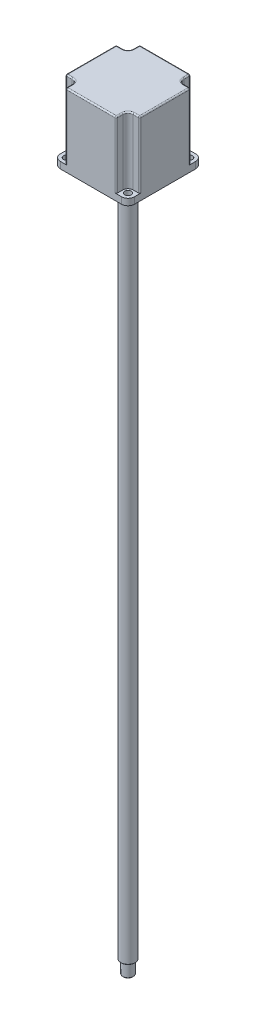
SolidWorks part; units mm, degrees
note: '?' marks a value the reader was unsure of.
material "1023 Carbon Steel Sheet (SS)"
ref_plane "Front" through (0, 0, 0) normal (0, 0, 1) x (1, 0, 0)
ref_plane "Top" through (0, 0, 0) normal (0, 1, 0) x (1, 0, 0)
ref_plane "Right" through (0, 0, 0) normal (1, 0, 0) x (0, 0, -1)
ref_axis "Axis1" through (-84.4107, 0, 0) along (1, 0, 0)?
ref_axis "Axis2" through (0, 64.3378, 0) along (0, -1, 0)?
ref_axis "Axis3" through (0, 0, -102.329) along (0, 0, 1)?
sketch "Sketch1" plane through (0, 0, 0) normal (0, 1, 0) x (1, 0, 0)
  line L1 (-28.5, -28.5) -> (28.5, -28.5)
  line L2 (-28.5, -28.5) -> (-28.5, 28.5)
  line L3 (-28.5, 28.5) -> (28.5, 28.5)
  line L4 (28.5, -28.5) -> (28.5, 28.5)
  line L5 (-28.5, -28.5) -> (28.5, 28.5) construction
  line L6 (-28.5, 28.5) -> (28.5, -28.5) construction
  point P0 (0, 0)
  dimension "D1" = 57
  dimension "D2" = 57
extrude "Extrude1" add sketch "Sketch1" along normal blind 76
hole_wizard "Ø5.0 (5) Diameter Hole1" positions "Sketch5" profile "Sketch4" hole size "Ø5.0" standard "ISO" end condition through all
sketch "Sketch5" plane through (0, 0, 0) normal (0, -1, 0) x (1, 0, 0)
  line L0 (-28.5, 28.5) -> (28.5, -28.5) construction
  line L3 (28.5, 28.5) -> (-28.5, -28.5) construction
  point P0 (-23.5, 23.5)
  point P1 (23.5, 23.5)
  point P3 (23.5, -23.5)
  point P5 (-23.5, -23.5)
  dimension "D1" = 47
  dimension "D2" = 47
sketch "Sketch4" plane through (-23.5, 0, 23.5) normal (1, 0, 0) x (0, 0, -1)
  line L0 (0, 0) -> (0, 76)
  line L1 (0, 76) -> (2.5, 76)
  line L2 (2.5, 76) -> (2.5, 0)
  line L5 (2.5, 0) -> (0, 0)
  line L11 (0, -6.35) -> (0, 107.95) construction
  dimension "Thru Hole Dia." = 5
  dimension "Thru Hole Depth" = 76
sketch "Sketch6" plane through (0, 76, 0) normal (0, 1, 0) x (1, 0, 0)
  line L0 (-19.5, 23.5) -> (-19.5, 32.5117)
  line L1 (-19.5, 32.5117) -> (-33.9089, 32.5117)
  line L2 (-33.9089, 32.5117) -> (-33.9089, 19.5)
  line L3 (-33.9089, 19.5) -> (-23.5, 19.5)
  line L4 (19.5, 23.5) -> (19.5, 36.4716)
  line L5 (19.5, 36.4716) -> (41.1684, 36.4716)
  line L6 (41.1684, 36.4716) -> (41.1684, 19.5)
  line L7 (41.1684, 19.5) -> (23.5, 19.5)
  line L8 (23.5, -19.5) -> (44.2522, -19.5)
  line L9 (44.2522, -19.5) -> (44.2522, -40.0504)
  line L10 (44.2522, -40.0504) -> (19.5, -40.0504)
  line L11 (19.5, -40.0504) -> (19.5, -23.5)
  line L12 (-23.5, -19.5) -> (-37.6708, -19.5)
  line L13 (-37.6708, -19.5) -> (-37.6708, -37.8282)
  line L14 (-37.6708, -37.8282) -> (-19.5, -37.8282)
  line L15 (-19.5, -37.8282) -> (-19.5, -23.5)
  circle A0 centre (-23.5, 23.5) radius 4
  circle A1 centre (23.5, 23.5) radius 4
  circle A2 centre (23.5, -23.5) radius 4
  circle A3 centre (-23.5, -23.5) radius 4
  circle M1 centre (-23.5, -23.5) radius 2.5
  circle M2 centre (23.5, -23.5) radius 2.5
  circle M3 centre (23.5, 23.5) radius 2.5
  circle M4 centre (-23.5, 23.5) radius 2.5
  line M5 (28.5, -28.5) -> (28.5, 28.5)
  line M6 (28.5, 28.5) -> (-28.5, 28.5)
  line M7 (-28.5, 28.5) -> (-28.5, -28.5)
  line M8 (-28.5, -28.5) -> (28.5, -28.5)
  dimension "D1" = 8
  dimension "D2" = 8
  dimension "D3" = 8
  dimension "D4" = 8
extrude "Extrude4" cut sketch "Sketch6" against normal blind 71 contours L2 L3 L0 L1 M7 M6 | A0 L0 L3 M6 M7 | A0 M4 | L7 L6 L5 L4 M6 M5 | A1 L7 L4 M5 M6 | A1 M3 | A2 M2 | A2 L11 L8 M8 M5 | L11 L10 L9 L8 M5 M8 | L14 L15 L12 L13 M8 M7 | A3 L12 L15 M7 M8 | A3 M1
fillet "Fillet1" radius 5 4 edges at (-28.5, 2.5, 28.5) (28.5, 2.5, 28.5) (28.5, 2.5, -28.5) (-28.5, 2.5, -28.5)
sketch "Sketch7" plane through (0, 76, 0) normal (0, 1, 0) x (1, 0, 0)
  circle A0 centre (0, 0) radius 3
  dimension "D1" = 6
extrude "Extrude5" add sketch "Sketch7" against normal blind 101 separate body
sketch "Sketch8" plane through (0, 0, 0) normal (0, -1, 0) x (1, 0, 0)
  circle A0 centre (0, 0) radius 19.05
  dimension "D1" = 38.1
extrude "Extrude6" add sketch "Sketch8" along normal blind 3
fillet "Fillet2" radius 1 24 edges at (-26, 76, 19.5) (-20.6716, 76, 20.6716) (-19.5, 76, 26) (0, 76, 28.5) (19.5, 76, 26) (20.6716, 76, 20.6716) (26, 76, 19.5) (28.5, 76, 0) (19.5, 76, -26) (26, 76, -19.5) (20.6716, 76, -20.6716) (-26, 76, -19.5) (-19.5, 76, -26) (-20.6716, 76, -20.6716) (0, 76, -28.5) (-28.5, 76, 0) (-19.5, 40.5, 28.5) (-28.5, 40.5, 19.5) (-28.5, 40.5, -19.5) (-19.5, 40.5, -28.5) (19.5, 40.5, -28.5) (28.5, 40.5, -19.5) (28.5, 40.5, 19.5) (19.5, 40.5, 28.5)
sketch "Sketch9" plane through (0, 0, 0) normal (0, -1, 0) x (1, 0, 0)
  circle A0 centre (0, 0) radius 5.5
  dimension "D1" = 11
extrude "Boss-Extrude1" add sketch "Sketch9" along normal blind 528
chamfer "Chamfer1" distance 0.5 angle 45 1 edges at (0, -528, -5.5)
sketch "Sketch10" plane through (0, -528, 0) normal (0, -1, 0) x (1, 0, 0)
  circle A0 centre (0, 0) radius 4
  dimension "D1" = 8
extrude "Boss-Extrude2" add sketch "Sketch10" along normal blind 10
chamfer "Chamfer2" distance 0.5 angle 45 1 edges at (0, -538, -4)
sketch "Sketch11" plane through (0, 0, 28.5) normal (0, 0, 1) x (1, 0, 0)
  line L0 (-23.5, 0) -> (23.5, 0) construction
  line L1 (42.7332, 56) -> (-106.5458, 56)
  line L2 (42.7332, 56) -> (42.7332, 147.9775)
  line L3 (42.7332, 147.9775) -> (-106.5458, 147.9775)
  line L4 (-106.5458, 56) -> (-106.5458, 147.9775)
  dimension "D1" = 56
extrude "Cut-Extrude1" cut sketch "Sketch11" against normal up to next
fillet "Fillet3" radius 1 24 edges at (19.2071, 56, 28.2071) (0, 56, 28.5) (-19.2071, 56, 28.2071) (-19.5, 56, 25.5) (-20.6716, 56, 20.6716) (-25.5, 56, 19.5) (-28.2071, 56, 19.2071) (-28.5, 56, 0) (-28.2071, 56, -19.2071) (-25.5, 56, -19.5) (-20.6716, 56, -20.6716) (-19.5, 56, -25.5) (-19.2071, 56, -28.2071) (0, 56, -28.5) (19.2071, 56, -28.2071) (19.5, 56, -25.5) (20.6716, 56, -20.6716) (25.5, 56, -19.5) (28.2071, 56, -19.2071) (28.5, 56, 0) (28.2071, 56, 19.2071) (25.5, 56, 19.5) (20.6716, 56, 20.6716) (19.5, 56, 25.5)
